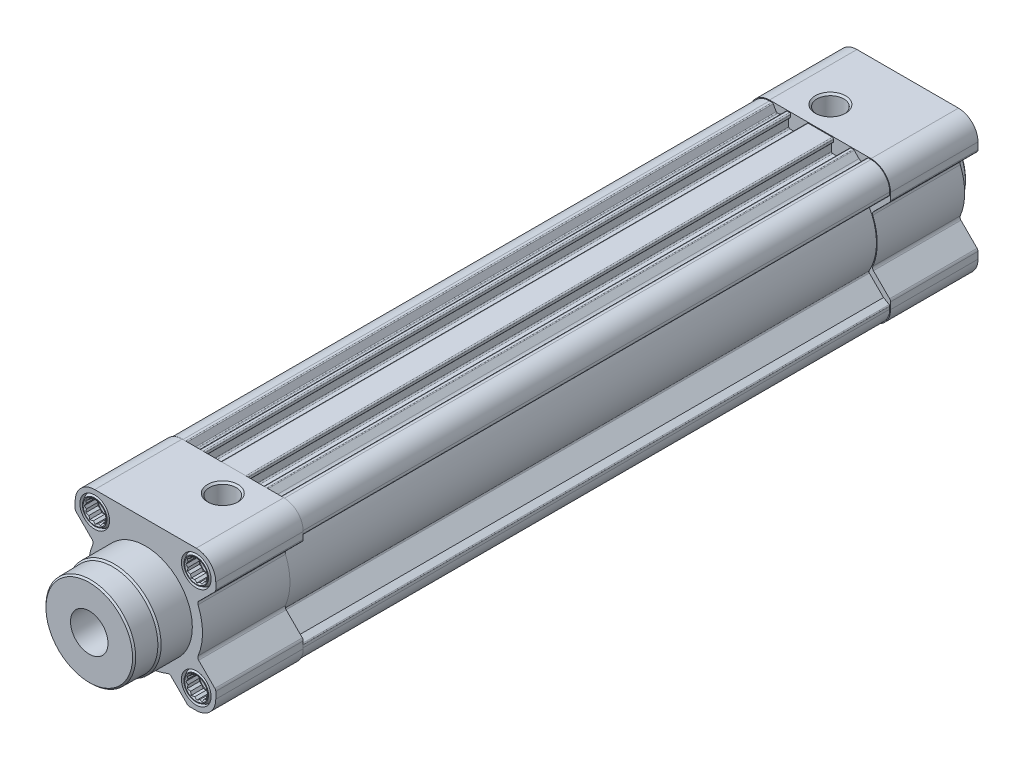
SolidWorks part; units mm, degrees
ref_plane "Front Plane" through (0, 0, 0) normal (0, 0, 1) x (1, 0, 0)
ref_plane "Top Plane" through (0, 0, 0) normal (0, 1, 0) x (1, 0, 0)
ref_plane "Right Plane" through (0, 0, 0) normal (1, 0, 0) x (0, 0, -1)
ref_plane "Plane1" through (0, 0, -28) normal (0, 0, 1) x (1, 0, 0)
sketch "Sketch1" plane through (0, 0, -28) normal (0, 0, 1) x (1, 0, 0)
  line L0 (-22.2071, 13.3683) -> (-17.0289, 8.1901)
  line L1 (-17.0289, -8.1901) -> (-22.2071, -13.3683)
  line L2 (-22.5, -14.0754) -> (-22.5, -16.25)
  line L3 (-16.25, -22.5) -> (-14.0754, -22.5)
  line L4 (-13.3683, -22.2071) -> (-8.1901, -17.0289)
  line L5 (8.1901, -17.0289) -> (13.3683, -22.2071)
  line L6 (14.0754, -22.5) -> (16.25, -22.5)
  line L7 (22.5, -16.25) -> (22.5, -14.0754)
  line L8 (22.2071, -13.3683) -> (17.0289, -8.1901)
  line L9 (17.0289, 8.1901) -> (22.2071, 13.3683)
  line L10 (22.5, 14.0754) -> (22.5, 16.25)
  line L11 (16.25, 22.5) -> (-16.25, 22.5)
  line L12 (-22.5, 16.25) -> (-22.5, 14.0754)
  arc A0 (-22.5, 14.0754) -> (-22.2071, 13.3683) centre (-21.5, 14.0754) ccw
  arc A1 (-17.0289, 8.1901) -> (-16.8147, 7.0943) centre (-17.736, 7.483) cw
  arc A2 (-16.8147, 7.0943) -> (-16.8147, -7.0943) centre (0, 0) ccw
  arc A3 (-16.8147, -7.0943) -> (-17.0289, -8.1901) centre (-17.736, -7.483) cw
  arc A4 (-22.2071, -13.3683) -> (-22.5, -14.0754) centre (-21.5, -14.0754) ccw
  arc A5 (-22.5, -16.25) -> (-16.25, -22.5) centre (-16.25, -16.25) ccw
  arc A6 (-14.0754, -22.5) -> (-13.3683, -22.2071) centre (-14.0754, -21.5) ccw
  arc A7 (-8.1901, -17.0289) -> (-7.0943, -16.8147) centre (-7.483, -17.736) cw
  arc A8 (-7.0943, -16.8147) -> (7.0943, -16.8147) centre (0, 0) ccw
  arc A9 (7.0943, -16.8147) -> (8.1901, -17.0289) centre (7.483, -17.736) cw
  arc A10 (13.3683, -22.2071) -> (14.0754, -22.5) centre (14.0754, -21.5) ccw
  arc A11 (16.25, -22.5) -> (22.5, -16.25) centre (16.25, -16.25) ccw
  arc A12 (22.5, -14.0754) -> (22.2071, -13.3683) centre (21.5, -14.0754) ccw
  arc A13 (17.0289, -8.1901) -> (16.8147, -7.0943) centre (17.736, -7.483) cw
  arc A14 (16.8147, -7.0943) -> (16.8147, 7.0943) centre (0, 0) ccw
  arc A15 (16.8147, 7.0943) -> (17.0289, 8.1901) centre (17.736, 7.483) cw
  arc A16 (22.2071, 13.3683) -> (22.5, 14.0754) centre (21.5, 14.0754) ccw
  arc A17 (22.5, 16.25) -> (16.25, 22.5) centre (16.25, 16.25) ccw
  arc A18 (-16.25, 22.5) -> (-22.5, 16.25) centre (-16.25, 16.25) ccw
extrude "Boss-Extrude1" add sketch "Sketch1" along normal blind 28
sketch "Sketch2" plane through (0, 0, -28) normal (0, 0, 1) x (1, 0, 0)
  line L0 (-22.25, 13.7647) -> (-16.641, 8.1557)
  line L1 (-16.641, -8.1557) -> (-22.25, -13.7647)
  line L2 (-22.25, -13.7647) -> (-22.25, -16.25)
  line L3 (-16.25, -22.25) -> (-13.7647, -22.25)
  line L4 (-13.7647, -22.25) -> (-8.1557, -16.641)
  line L5 (8.1557, -16.641) -> (13.7647, -22.25)
  line L6 (13.7647, -22.25) -> (16.25, -22.25)
  line L7 (22.25, -16.25) -> (22.25, -13.7647)
  line L8 (22.25, -13.7647) -> (16.641, -8.1557)
  line L9 (16.641, 8.1557) -> (22.25, 13.7647)
  line L10 (22.25, 13.7647) -> (22.25, 16.25)
  line L11 (16.25, 22.25) -> (-16.25, 22.25)
  line L12 (-22.25, 16.25) -> (-22.25, 13.7647)
  arc A0 (-16.641, 8.1557) -> (-16.5402, 7.5936) centre (-16.9946, 7.8022) cw
  arc A1 (-16.5402, 7.5936) -> (-16.5402, -7.5936) centre (0, 0) ccw
  arc A2 (-16.5402, -7.5936) -> (-16.641, -8.1557) centre (-16.9946, -7.8022) cw
  arc A3 (-22.25, -16.25) -> (-16.25, -22.25) centre (-16.25, -16.25) ccw
  arc A4 (-8.1557, -16.641) -> (-7.5936, -16.5402) centre (-7.8022, -16.9946) cw
  arc A5 (-7.5936, -16.5402) -> (7.5936, -16.5402) centre (0, 0) ccw
  arc A6 (7.5936, -16.5402) -> (8.1557, -16.641) centre (7.8022, -16.9946) cw
  arc A7 (16.25, -22.25) -> (22.25, -16.25) centre (16.25, -16.25) ccw
  arc A8 (16.641, -8.1557) -> (16.5402, -7.5936) centre (16.9946, -7.8022) cw
  arc A9 (16.5402, -7.5936) -> (16.5402, 7.5936) centre (0, 0) ccw
  arc A10 (16.5402, 7.5936) -> (16.641, 8.1557) centre (16.9946, 7.8022) cw
  arc A11 (22.25, 16.25) -> (16.25, 22.25) centre (16.25, 16.25) ccw
  arc A12 (-16.25, 22.25) -> (-22.25, 16.25) centre (-16.25, 16.25) ccw
extrude "Boss-Extrude2" add sketch "Sketch2" against normal blind 188
sketch "Sketch3" plane through (0, 0, -28) normal (0, 0, 1) x (1, 0, 0)
  line L0 (-27, -27) -> (27, -27)
  line L1 (27, -27) -> (27, 27)
  line L2 (27, 27) -> (-27, 27)
  line L3 (-27, 27) -> (-27, -27)
  line L4 (-22.05, 15.0635) -> (-20.288, 14.0462)
  line L5 (-20.2051, 13.9826) -> (-15.7255, 9.503)
  line L6 (-15.7255, -9.503) -> (-20.2424, -14.0198)
  line L7 (-20.2424, -14.0198) -> (-22.05, -15.0635)
  line L8 (-22.25, -15.4099) -> (-22.25, -16.25)
  line L9 (-16.25, -22.25) -> (-15.4099, -22.25)
  line L10 (-15.0635, -22.05) -> (-14.0462, -20.288)
  line L11 (-13.9826, -20.2051) -> (-9.503, -15.7255)
  line L12 (9.503, -15.7255) -> (13.9826, -20.2051)
  line L13 (14.0462, -20.288) -> (15.0635, -22.05)
  line L14 (15.4099, -22.25) -> (16.25, -22.25)
  line L15 (22.25, -16.25) -> (22.25, -15.4099)
  line L16 (22.05, -15.0635) -> (20.2424, -14.0198)
  line L17 (20.2424, -14.0198) -> (15.7255, -9.503)
  line L18 (15.7255, 9.503) -> (20.2051, 13.9826)
  line L19 (20.288, 14.0462) -> (22.05, 15.0635)
  line L20 (22.25, 15.4099) -> (22.25, 16.25)
  line L21 (16.25, 22.25) -> (15.4099, 22.25)
  line L22 (15.0635, 22.05) -> (14.082, 20.35)
  line L23 (13.7356, 20.15) -> (13.4713, 20.15)
  line L24 (12.4107, 20.5893) -> (10.8672, 22.1328)
  line L25 (10.5843, 22.25) -> (9.85, 22.25)
  line L26 (9.45, 21.85) -> (9.45, 21.15)
  line L27 (9.65, 20.95) -> (9.9, 20.95)
  line L28 (10.1, 20.75) -> (10.1, 18.15)
  line L29 (9.7, 17.75) -> (4, 17.75)
  line L30 (3.6, 18.15) -> (3.6, 20.75)
  line L31 (3.8, 20.95) -> (4.05, 20.95)
  line L32 (4.25, 21.15) -> (4.25, 21.85)
  line L33 (3.85, 22.25) -> (-3.85, 22.25)
  line L34 (-4.25, 21.85) -> (-4.25, 21.15)
  line L35 (-4.05, 20.95) -> (-3.8, 20.95)
  line L36 (-3.6, 20.75) -> (-3.6, 18.15)
  line L37 (-4, 17.75) -> (-9.7, 17.75)
  line L38 (-10.1, 18.15) -> (-10.1, 20.75)
  line L39 (-9.9, 20.95) -> (-9.65, 20.95)
  line L40 (-9.45, 21.15) -> (-9.45, 21.85)
  line L41 (-9.85, 22.25) -> (-10.5843, 22.25)
  line L42 (-10.8672, 22.1328) -> (-12.4107, 20.5893)
  line L43 (-13.4713, 20.15) -> (-13.7356, 20.15)
  line L44 (-14.082, 20.35) -> (-15.0635, 22.05)
  line L45 (-15.4099, 22.25) -> (-16.25, 22.25)
  line L46 (-22.25, 16.25) -> (-22.25, 15.4099)
  arc A0 (-22.25, 15.4099) -> (-22.05, 15.0635) centre (-21.85, 15.4099) ccw
  arc A1 (-20.288, 14.0462) -> (-20.2051, 13.9826) centre (-20.488, 13.6997) cw
  arc A2 (-15.7255, 9.503) -> (-15.6445, 8.9022) centre (-16.0791, 9.1495) cw
  arc A3 (-15.6445, 8.9022) -> (-15.6445, -8.9022) centre (0, 0) ccw
  arc A4 (-15.6445, -8.9022) -> (-15.7255, -9.503) centre (-16.0791, -9.1495) cw
  arc A5 (-22.05, -15.0635) -> (-22.25, -15.4099) centre (-21.85, -15.4099) ccw
  arc A6 (-22.25, -16.25) -> (-16.25, -22.25) centre (-16.25, -16.25) ccw
  arc A7 (-15.4099, -22.25) -> (-15.0635, -22.05) centre (-15.4099, -21.85) ccw
  arc A8 (-14.0462, -20.288) -> (-13.9826, -20.2051) centre (-13.6997, -20.488) cw
  arc A9 (-9.503, -15.7255) -> (-8.9022, -15.6445) centre (-9.1495, -16.0791) cw
  arc A10 (-8.9022, -15.6445) -> (8.9022, -15.6445) centre (0, 0) ccw
  arc A11 (8.9022, -15.6445) -> (9.503, -15.7255) centre (9.1495, -16.0791) cw
  arc A12 (13.9826, -20.2051) -> (14.0462, -20.288) centre (13.6997, -20.488) cw
  arc A13 (15.0635, -22.05) -> (15.4099, -22.25) centre (15.4099, -21.85) ccw
  arc A14 (16.25, -22.25) -> (22.25, -16.25) centre (16.25, -16.25) ccw
  arc A15 (22.25, -15.4099) -> (22.05, -15.0635) centre (21.85, -15.4099) ccw
  arc A16 (15.7255, -9.503) -> (15.6445, -8.9022) centre (16.0791, -9.1495) cw
  arc A17 (15.6445, -8.9022) -> (15.6445, 8.9022) centre (0, 0) ccw
  arc A18 (15.6445, 8.9022) -> (15.7255, 9.503) centre (16.0791, 9.1495) cw
  arc A19 (20.2051, 13.9826) -> (20.288, 14.0462) centre (20.488, 13.6997) cw
  arc A20 (22.05, 15.0635) -> (22.25, 15.4099) centre (21.85, 15.4099) ccw
  arc A21 (22.25, 16.25) -> (16.25, 22.25) centre (16.25, 16.25) ccw
  arc A22 (15.4099, 22.25) -> (15.0635, 22.05) centre (15.4099, 21.85) ccw
  arc A23 (14.082, 20.35) -> (13.7356, 20.15) centre (13.7356, 20.55) cw
  arc A24 (13.4713, 20.15) -> (12.4107, 20.5893) centre (13.4713, 21.65) cw
  arc A25 (10.8672, 22.1328) -> (10.5843, 22.25) centre (10.5843, 21.85) ccw
  arc A26 (9.85, 22.25) -> (9.45, 21.85) centre (9.85, 21.85) ccw
  arc A27 (9.45, 21.15) -> (9.65, 20.95) centre (9.65, 21.15) ccw
  arc A28 (9.9, 20.95) -> (10.1, 20.75) centre (9.9, 20.75) cw
  arc A29 (10.1, 18.15) -> (9.7, 17.75) centre (9.7, 18.15) cw
  arc A30 (4, 17.75) -> (3.6, 18.15) centre (4, 18.15) cw
  arc A31 (3.6, 20.75) -> (3.8, 20.95) centre (3.8, 20.75) cw
  arc A32 (4.05, 20.95) -> (4.25, 21.15) centre (4.05, 21.15) ccw
  arc A33 (4.25, 21.85) -> (3.85, 22.25) centre (3.85, 21.85) ccw
  arc A34 (-3.85, 22.25) -> (-4.25, 21.85) centre (-3.85, 21.85) ccw
  arc A35 (-4.25, 21.15) -> (-4.05, 20.95) centre (-4.05, 21.15) ccw
  arc A36 (-3.8, 20.95) -> (-3.6, 20.75) centre (-3.8, 20.75) cw
  arc A37 (-3.6, 18.15) -> (-4, 17.75) centre (-4, 18.15) cw
  arc A38 (-9.7, 17.75) -> (-10.1, 18.15) centre (-9.7, 18.15) cw
  arc A39 (-10.1, 20.75) -> (-9.9, 20.95) centre (-9.9, 20.75) cw
  arc A40 (-9.65, 20.95) -> (-9.45, 21.15) centre (-9.65, 21.15) ccw
  arc A41 (-9.45, 21.85) -> (-9.85, 22.25) centre (-9.85, 21.85) ccw
  arc A42 (-10.5843, 22.25) -> (-10.8672, 22.1328) centre (-10.5843, 21.85) ccw
  arc A43 (-12.4107, 20.5893) -> (-13.4713, 20.15) centre (-13.4713, 21.65) cw
  arc A44 (-13.7356, 20.15) -> (-14.082, 20.35) centre (-13.7356, 20.55) cw
  arc A45 (-15.0635, 22.05) -> (-15.4099, 22.25) centre (-15.4099, 21.85) ccw
  arc A46 (-16.25, 22.25) -> (-22.25, 16.25) centre (-16.25, 16.25) ccw
extrude "Cut-Extrude1" cut sketch "Sketch3" against normal blind 188
ref_plane "Plane2" through (0, 0, -244) normal (0, 0, 1) x (1, 0, 0)
sketch "Sketch4" plane through (0, 0, -244) normal (0, 0, 1) x (1, 0, 0)
  line L0 (-22.2071, 13.3683) -> (-17.0289, 8.1901)
  line L1 (-17.0289, -8.1901) -> (-22.2071, -13.3683)
  line L2 (-22.5, -14.0754) -> (-22.5, -16.25)
  line L3 (-16.25, -22.5) -> (-14.0754, -22.5)
  line L4 (-13.3683, -22.2071) -> (-8.1901, -17.0289)
  line L5 (8.1901, -17.0289) -> (13.3683, -22.2071)
  line L6 (14.0754, -22.5) -> (16.25, -22.5)
  line L7 (22.5, -16.25) -> (22.5, -14.0754)
  line L8 (22.2071, -13.3683) -> (17.0289, -8.1901)
  line L9 (17.0289, 8.1901) -> (22.2071, 13.3683)
  line L10 (22.5, 14.0754) -> (22.5, 16.25)
  line L11 (16.25, 22.5) -> (-16.25, 22.5)
  line L12 (-22.5, 16.25) -> (-22.5, 14.0754)
  arc A0 (-22.5, 14.0754) -> (-22.2071, 13.3683) centre (-21.5, 14.0754) ccw
  arc A1 (-17.0289, 8.1901) -> (-16.8147, 7.0943) centre (-17.736, 7.483) cw
  arc A2 (-16.8147, 7.0943) -> (-16.8147, -7.0943) centre (0, 0) ccw
  arc A3 (-16.8147, -7.0943) -> (-17.0289, -8.1901) centre (-17.736, -7.483) cw
  arc A4 (-22.2071, -13.3683) -> (-22.5, -14.0754) centre (-21.5, -14.0754) ccw
  arc A5 (-22.5, -16.25) -> (-16.25, -22.5) centre (-16.25, -16.25) ccw
  arc A6 (-14.0754, -22.5) -> (-13.3683, -22.2071) centre (-14.0754, -21.5) ccw
  arc A7 (-8.1901, -17.0289) -> (-7.0943, -16.8147) centre (-7.483, -17.736) cw
  arc A8 (-7.0943, -16.8147) -> (7.0943, -16.8147) centre (0, 0) ccw
  arc A9 (7.0943, -16.8147) -> (8.1901, -17.0289) centre (7.483, -17.736) cw
  arc A10 (13.3683, -22.2071) -> (14.0754, -22.5) centre (14.0754, -21.5) ccw
  arc A11 (16.25, -22.5) -> (22.5, -16.25) centre (16.25, -16.25) ccw
  arc A12 (22.5, -14.0754) -> (22.2071, -13.3683) centre (21.5, -14.0754) ccw
  arc A13 (17.0289, -8.1901) -> (16.8147, -7.0943) centre (17.736, -7.483) cw
  arc A14 (16.8147, -7.0943) -> (16.8147, 7.0943) centre (0, 0) ccw
  arc A15 (16.8147, 7.0943) -> (17.0289, 8.1901) centre (17.736, 7.483) cw
  arc A16 (22.2071, 13.3683) -> (22.5, 14.0754) centre (21.5, 14.0754) ccw
  arc A17 (22.5, 16.25) -> (16.25, 22.5) centre (16.25, 16.25) ccw
  arc A18 (-16.25, 22.5) -> (-22.5, 16.25) centre (-16.25, 16.25) ccw
extrude "Boss-Extrude3" add sketch "Sketch4" along normal blind 28
sketch "Sketch5" plane through (0, 0, 0) normal (1, 0, 0) x (0, 0, -1)
  line L0 (-18, 0) -> (-18, 13.8691)
  line L1 (-18, 13.8691) -> (-17.5, 14.3691)
  line L2 (-17.5, 14.3691) -> (-10.5089, 14.4911)
  line L3 (-10.5089, 14.4911) -> (-10, 15)
  line L4 (-10, 15) -> (0, 15)
  line L5 (0, 15) -> (0, 0)
  line L6 (0, 0) -> (-18, 0)
  line L7 (0, 0) -> (-18, 0) construction
revolve "Revolve1" add sketch "Sketch5" angle 360 about L7 reverse direction yes
ref_plane "Plane3" through (5.25, 0, 0) normal (1, 0, 0) x (0, 0, -1)
sketch "Sketch6" plane through (5.25, 0, 0) normal (1, 0, 0) x (0, 0, -1)
  line L0 (19.5, 22.5) -> (24.364, 22.5)
  line L1 (24.364, 22.5) -> (23.783, 21.919)
  line L2 (23.783, 21.919) -> (23.783, 0)
  line L3 (23.783, 0) -> (19.5, 0)
  line L4 (19.5, 0) -> (19.5, 22.5)
  line L5 (19.5, 0) -> (19.5, 22.5) construction
revolve "Cut-Revolve1" cut sketch "Sketch6" angle 360 about L5 reverse direction yes
cosmetic thread "Cosmetic Thread1" parameters "D1"=10, "D2"=9.728
ref_plane "Plane4" through (-5.7, 0, 0) normal (1, 0, 0) x (0, 0, -1)
ref_plane "Plane5" through (16.25, 0, 0) normal (1, 0, 0) x (0, 0, -1)
sketch "Sketch7" plane through (16.25, 0, 0) normal (1, 0, 0) x (0, 0, -1)
  line L0 (0, 16.25) -> (0, 21)
  line L1 (0, 21) -> (21, 21)
  line L2 (21, 21) -> (21, 16.25)
  line L3 (21, 16.25) -> (0, 16.25)
  line L4 (21, 16.25) -> (0, 16.25) construction
revolve "Cut-Revolve2" cut sketch "Sketch7" angle 360 about L4 reverse direction yes
sketch "Sketch8" plane through (0, 0, 0) normal (0, 0, 1) x (1, 0, 0)
  line L0 (16.25, 16.25) -> (-16.25, 16.25)
  line L1 (16.25, 16.25) -> (16.25, -16.25)
pattern_linear "LPattern1" count 2 spacing 32.5 along (-1, 0, 0) count 2 spacing 32.5 along (0, -1, 0) of "Cut-Revolve2"
sketch "Sketch9" plane through (16.25, 0, 0) normal (1, 0, 0) x (0, 0, -1)
  line L0 (0, 16.25) -> (0, 20.1726)
  line L1 (0, 20.1726) -> (1, 20.75)
  line L2 (1, 20.75) -> (21, 20.75)
  line L3 (21, 20.75) -> (21, 16.25)
  line L4 (21, 16.25) -> (0, 16.25)
  line L5 (21, 16.25) -> (0, 16.25) construction
revolve "Revolve2" add sketch "Sketch9" angle 360 about L5 reverse direction yes
sketch "Sketch10" plane through (0, 0, 0) normal (0, 0, 1) x (1, 0, 0)
  line L0 (16.25, 16.25) -> (-16.25, 16.25)
  line L1 (16.25, 16.25) -> (16.25, -16.25)
pattern_linear "LPattern2" count 2 spacing 32.5 along (-1, 0, 0) count 2 spacing 32.5 along (0, -1, 0) of "Revolve2"
sketch "Sketch11" plane through (16.25, 0, 0) normal (1, 0, 0) x (0, 0, -1)
  line L0 (0, 16.25) -> (0, 19.95)
  line L1 (0, 19.95) -> (0.4041, 19.25)
  line L2 (0.4041, 19.25) -> (5.5, 19.25)
  line L3 (5.5, 19.25) -> (6.0415, 18.7085)
  line L4 (6.0415, 18.7085) -> (18.7, 18.7085)
  line L5 (18.7, 18.7085) -> (20.1194, 16.25)
  line L6 (20.1194, 16.25) -> (0, 16.25)
  line L7 (20.1194, 16.25) -> (0, 16.25) construction
revolve "Cut-Revolve3" cut sketch "Sketch11" angle 360 about L7 reverse direction yes
cosmetic thread "Cosmetic Thread2" parameters "D1"=10.5, "D2"=6
sketch "Sketch12" plane through (0, 0, 0) normal (0, 0, 1) x (1, 0, 0)
  line L0 (12.7859, 16.25) -> (13.25, 15.4462)
  line L1 (13.25, 15.4462) -> (13.25, 14.5179)
  line L2 (13.25, 14.5179) -> (14.0538, 14.0538)
  line L3 (14.0538, 14.0538) -> (14.5179, 13.25)
  line L4 (14.5179, 13.25) -> (15.4462, 13.25)
  line L5 (15.4462, 13.25) -> (16.25, 12.7859)
  line L6 (16.25, 12.7859) -> (17.0538, 13.25)
  line L7 (17.0538, 13.25) -> (17.9821, 13.25)
  line L8 (17.9821, 13.25) -> (18.4462, 14.0538)
  line L9 (18.4462, 14.0538) -> (19.25, 14.5179)
  line L10 (19.25, 14.5179) -> (19.25, 15.4462)
  line L11 (19.25, 15.4462) -> (19.7141, 16.25)
  line L12 (19.7141, 16.25) -> (19.25, 17.0538)
  line L13 (19.25, 17.0538) -> (19.25, 17.9821)
  line L14 (19.25, 17.9821) -> (18.4462, 18.4462)
  line L15 (18.4462, 18.4462) -> (17.9821, 19.25)
  line L16 (17.9821, 19.25) -> (17.0538, 19.25)
  line L17 (17.0538, 19.25) -> (16.25, 19.7141)
  line L18 (16.25, 19.7141) -> (15.4462, 19.25)
  line L19 (15.4462, 19.25) -> (14.5179, 19.25)
  line L20 (14.5179, 19.25) -> (14.0538, 18.4462)
  line L21 (14.0538, 18.4462) -> (13.25, 17.9821)
  line L22 (13.25, 17.9821) -> (13.25, 17.0538)
  line L23 (13.25, 17.0538) -> (12.7859, 16.25)
extrude "Cut-Extrude2" cut sketch "Sketch12" along normal blind 4 and the other way blind 4
sketch "Sketch13" plane through (0, 0, 0) normal (0, 0, 1) x (1, 0, 0)
  line L0 (16.25, 16.25) -> (-16.25, 16.25)
  line L1 (16.25, 16.25) -> (16.25, -16.25)
pattern_linear "LPattern3" count 2 spacing 32.5 along (-1, 0, 0) count 2 spacing 32.5 along (0, -1, 0) of "Cut-Revolve3"
cosmetic thread "Cosmetic Thread3" parameters "D1"=10.5, "D2"=6
cosmetic thread "Cosmetic Thread4" parameters "D1"=10.5, "D2"=6
cosmetic thread "Cosmetic Thread5" parameters "D1"=10.5, "D2"=6
sketch "Sketch14" plane through (0, 0, 0) normal (0, 0, 1) x (1, 0, 0)
  line L0 (16.25, 16.25) -> (-16.25, 16.25)
  line L1 (16.25, 16.25) -> (16.25, -16.25)
pattern_linear "LPattern4" count 2 spacing 32.5 along (-1, 0, 0) count 2 spacing 32.5 along (0, -1, 0) of "Cut-Extrude2"
ref_plane "Plane6" through (0, 0, -244) normal (0, 0, 1) x (1, 0, 0)
sketch "Sketch15" plane through (0, 0, 0) normal (1, 0, 0) x (0, 0, -1)
  line L0 (244, 0) -> (244, 15)
  line L1 (244, 15) -> (247.5, 15)
  line L2 (247.5, 15) -> (248, 14.5)
  line L3 (248, 14.5) -> (248, 0)
  line L4 (248, 0) -> (244, 0)
  line L5 (248, 0) -> (244, 0) construction
revolve "Revolve3" add sketch "Sketch15" angle 360 about L5 reverse direction yes
ref_plane "Plane7" through (-5.25, 0, 0) normal (1, 0, 0) x (0, 0, -1)
sketch "Sketch16" plane through (-5.25, 0, 0) normal (1, 0, 0) x (0, 0, -1)
  line L0 (224.5, 22.5) -> (229.364, 22.5)
  line L1 (229.364, 22.5) -> (228.783, 21.919)
  line L2 (228.783, 21.919) -> (228.783, 0)
  line L3 (228.783, 0) -> (224.5, 0)
  line L4 (224.5, 0) -> (224.5, 22.5)
  line L5 (224.5, 0) -> (224.5, 22.5) construction
revolve "Cut-Revolve4" cut sketch "Sketch16" angle 360 about L5 reverse direction yes
cosmetic thread "Cosmetic Thread6" parameters "D1"=10, "D2"=9.728
ref_plane "Plane8" through (5.7, 0, 0) normal (1, 0, 0) x (0, 0, -1)
sketch "Sketch17" plane through (16.25, 0, 0) normal (1, 0, 0) x (0, 0, -1)
  line L0 (223, 16.25) -> (223, 21)
  line L1 (223, 21) -> (244, 21)
  line L2 (244, 21) -> (244, 16.25)
  line L3 (244, 16.25) -> (223, 16.25)
  line L4 (244, 16.25) -> (223, 16.25) construction
revolve "Cut-Revolve5" cut sketch "Sketch17" angle 360 about L4 reverse direction yes
sketch "Sketch18" plane through (0, 0, -244) normal (0, 0, 1) x (1, 0, 0)
  line L0 (16.25, 16.25) -> (-16.25, 16.25)
  line L1 (16.25, 16.25) -> (16.25, -16.25)
pattern_linear "LPattern5" count 2 spacing 32.5 along (-1, 0, 0) count 2 spacing 32.5 along (0, -1, 0) of "Cut-Revolve5"
sketch "Sketch19" plane through (16.25, 0, 0) normal (1, 0, 0) x (0, 0, -1)
  line L0 (223, 16.25) -> (223, 20.75)
  line L1 (223, 20.75) -> (243, 20.75)
  line L2 (243, 20.75) -> (244, 20.1726)
  line L3 (244, 20.1726) -> (244, 16.25)
  line L4 (244, 16.25) -> (223, 16.25)
  line L5 (244, 16.25) -> (223, 16.25) construction
revolve "Revolve4" add sketch "Sketch19" angle 360 about L5 reverse direction yes
sketch "Sketch20" plane through (0, 0, -244) normal (0, 0, 1) x (1, 0, 0)
  line L0 (16.25, 16.25) -> (-16.25, 16.25)
  line L1 (16.25, 16.25) -> (16.25, -16.25)
pattern_linear "LPattern6" count 2 spacing 32.5 along (-1, 0, 0) count 2 spacing 32.5 along (0, -1, 0) of "Revolve4"
sketch "Sketch21" plane through (16.25, 0, 0) normal (1, 0, 0) x (0, 0, -1)
  line L0 (223.8806, 16.25) -> (225.3, 18.7085)
  line L1 (225.3, 18.7085) -> (237.9585, 18.7085)
  line L2 (237.9585, 18.7085) -> (238.5, 19.25)
  line L3 (238.5, 19.25) -> (243.5959, 19.25)
  line L4 (243.5959, 19.25) -> (244, 19.95)
  line L5 (244, 19.95) -> (244, 16.25)
  line L6 (244, 16.25) -> (223.8806, 16.25)
  line L7 (244, 16.25) -> (223.8806, 16.25) construction
revolve "Cut-Revolve6" cut sketch "Sketch21" angle 360 about L7 reverse direction yes
cosmetic thread "Cosmetic Thread7" parameters "D1"=10.5, "D2"=6
sketch "Sketch22" plane through (0, 0, -244) normal (0, 0, 1) x (1, 0, 0)
  line L0 (16.25, 16.25) -> (-16.25, 16.25)
  line L1 (16.25, 16.25) -> (16.25, -16.25)
pattern_linear "LPattern7" count 2 spacing 32.5 along (-1, 0, 0) count 2 spacing 32.5 along (0, -1, 0) of "Cut-Revolve6"
cosmetic thread "Cosmetic Thread8" parameters "D1"=10.5, "D2"=6
cosmetic thread "Cosmetic Thread9" parameters "D1"=10.5, "D2"=6
cosmetic thread "Cosmetic Thread10" parameters "D1"=10.5, "D2"=6
sketch "Sketch23" plane through (0, 0, -244) normal (0, 0, 1) x (1, 0, 0)
  line L0 (12.7859, 16.25) -> (13.25, 15.4462)
  line L1 (13.25, 15.4462) -> (13.25, 14.5179)
  line L2 (13.25, 14.5179) -> (14.0538, 14.0538)
  line L3 (14.0538, 14.0538) -> (14.5179, 13.25)
  line L4 (14.5179, 13.25) -> (15.4462, 13.25)
  line L5 (15.4462, 13.25) -> (16.25, 12.7859)
  line L6 (16.25, 12.7859) -> (17.0538, 13.25)
  line L7 (17.0538, 13.25) -> (17.9821, 13.25)
  line L8 (17.9821, 13.25) -> (18.4462, 14.0538)
  line L9 (18.4462, 14.0538) -> (19.25, 14.5179)
  line L10 (19.25, 14.5179) -> (19.25, 15.4462)
  line L11 (19.25, 15.4462) -> (19.7141, 16.25)
  line L12 (19.7141, 16.25) -> (19.25, 17.0538)
  line L13 (19.25, 17.0538) -> (19.25, 17.9821)
  line L14 (19.25, 17.9821) -> (18.4462, 18.4462)
  line L15 (18.4462, 18.4462) -> (17.9821, 19.25)
  line L16 (17.9821, 19.25) -> (17.0538, 19.25)
  line L17 (17.0538, 19.25) -> (16.25, 19.7141)
  line L18 (16.25, 19.7141) -> (15.4462, 19.25)
  line L19 (15.4462, 19.25) -> (14.5179, 19.25)
  line L20 (14.5179, 19.25) -> (14.0538, 18.4462)
  line L21 (14.0538, 18.4462) -> (13.25, 17.9821)
  line L22 (13.25, 17.9821) -> (13.25, 17.0538)
  line L23 (13.25, 17.0538) -> (12.7859, 16.25)
extrude "Cut-Extrude3" cut sketch "Sketch23" along normal blind 4 and the other way blind 4
sketch "Sketch24" plane through (0, 0, -244) normal (0, 0, 1) x (1, 0, 0)
  line L0 (16.25, 16.25) -> (-16.25, 16.25)
  line L1 (16.25, 16.25) -> (16.25, -16.25)
pattern_linear "LPattern8" count 2 spacing 32.5 along (-1, 0, 0) count 2 spacing 32.5 along (0, -1, 0) of "Cut-Extrude3"
ref_plane "Plane9" through (0, 0, 0) normal (0.7071, 0.7071, 0) x (0.7071, -0.7071, 0)
ref_plane "Plane10" through (0, 0, -254) normal (0, 0, 1) x (1, 0, 0)
ref_plane "Plane11" through (0, 0, -216) normal (0, 0, 1) x (1, 0, 0)
sketch "Sketch25" plane through (0, 0, 0) normal (1, 0, 0) x (0, 0, -1)
  line L0 (-18, 0) -> (-18, 6)
  line L1 (-18, 6) -> (55.3333, 6)
  line L2 (55.3333, 6) -> (55.3333, 16)
  line L3 (55.3333, 16) -> (216, 16)
  line L4 (216, 16) -> (216, 0)
  line L5 (216, 0) -> (-18, 0)
  line L6 (216, 0) -> (-18, 0) construction
revolve "Cut-Revolve7" cut sketch "Sketch25" angle 360 about L6 reverse direction yes
ref_plane "Plane12" through (0, 0, 18) normal (0, 0, 1) x (1, 0, 0)
ref_plane "Plane13" through (0, 0, 0) normal (0, 0, 1) x (1, 0, 0)
ref_plane "Plane14" through (0, 0, -244) normal (0, 0, 1) x (1, 0, 0)
ref_plane "Plane15" through (0, 0, -43) normal (0, 0, 1) x (1, 0, 0)
ref_plane "Plane16" through (0, 22.5, 0) normal (0, 1, 0) x (1, 0, 0)
ref_plane "Plane17" through (0, 0, -28) normal (0, 0, 1) x (1, 0, 0)
ref_plane "Plane18" through (0, 0, 0) normal (1, 0, 0) x (0, 0, -1)
ref_plane "Plane19" through (0, 22.5, 0) normal (0, 1, 0) x (1, 0, 0)
ref_plane "Plane20" through (0, 0, 0) normal (0, 0, 1) x (1, 0, 0)
ref_plane "Plane21" through (0, 0, -244) normal (0, 0, 1) x (1, 0, 0)
ref_plane "2DUMMY XY" through (0, 0, 0) normal (0, 0, -1) x (-1, 0, 0)
ref_plane "2DUMMY XZ" through (0, 0, 0) normal (0, 1, 0) x (1, 0, 0)
ref_plane "2DUMMY YZ" through (0, 0, 0) normal (1, 0, 0) x (0, 0, -1)
ref_axis "2DUMMY X" through (-80.9, 0, 0) along (1, 0, 0)
ref_axis "2DUMMY Y" through (0, 50, 0) along (0, -1, 0)
ref_axis "2DUMMY Z" through (0, 0, -80.9) along (0, 0, 1)
sketch3d "2DUMMY"
  point P0 (0, 0, 0)
ref_plane "2P XY" through (0, 0, -216) normal (0, 0, 1) x (1, 0, 0)
ref_plane "2P XZ" through (0, 0, 0) normal (0, -1, 0) x (-1, 0, 0)
ref_plane "2P YZ" through (0, 0, 0) normal (1, 0, 0) x (0, 0, -1)
ref_axis "2P X" through (-80.9, 0, -216) along (1, 0, 0)
ref_axis "2P Y" through (0, -50, -216) along (0, 1, 0)
ref_axis "2P Z" through (0, 0, 80.9) along (0, 0, -1)
sketch3d "2P"
  point P0 (0, 0, -216)
ref_plane "FDT_FRONT XY" through (0, 0, 0) normal (0, 0, 1) x (1, 0, 0)
ref_plane "FDT_FRONT XZ" through (0, 0, 0) normal (0, -1, 0) x (-1, 0, 0)
ref_plane "FDT_FRONT YZ" through (0, 0, 0) normal (1, 0, 0) x (0, 0, -1)
ref_axis "FDT_FRONT X" through (-80.9, 0, 0) along (1, 0, 0)
ref_axis "FDT_FRONT Y" through (0, -50, 0) along (0, 1, 0)
ref_axis "FDT_FRONT Z" through (0, 0, 80.9) along (0, 0, -1)
sketch3d "FDT_FRONT"
  point P0 (0, 0, 0)
ref_plane "FDT_QSFRONT XY" through (0, 22.5, 0) normal (0, 1, 0) x (1, 0, 0)
ref_plane "FDT_QSFRONT XZ" through (0, 0, -19.5) normal (0, 0, 1) x (1, 0, 0)
ref_plane "FDT_QSFRONT YZ" through (5.25, 0, 0) normal (1, 0, 0) x (0, 0, -1)
ref_axis "FDT_QSFRONT X" through (-80.9, 22.5, -19.5) along (1, 0, 0)
ref_axis "FDT_QSFRONT Y" through (5.25, 22.5, 50) along (0, 0, -1)
ref_axis "FDT_QSFRONT Z" through (5.25, 50, -19.5) along (0, -1, 0)
sketch3d "FDT_QSFRONT"
  point P0 (5.25, 22.5, -19.5)
ref_plane "FDT_QSREAR XY" through (0, 22.5, 0) normal (0, 1, 0) x (1, 0, 0)
ref_plane "FDT_QSREAR XZ" through (0, 0, -224.5) normal (0, 0, 1) x (1, 0, 0)
ref_plane "FDT_QSREAR YZ" through (-5.25, 0, 0) normal (1, 0, 0) x (0, 0, -1)
ref_axis "FDT_QSREAR X" through (-80.9, 22.5, -224.5) along (1, 0, 0)
ref_axis "FDT_QSREAR Y" through (-5.25, 22.5, 50) along (0, 0, -1)
ref_axis "FDT_QSREAR Z" through (-5.25, 50, -224.5) along (0, -1, 0)
sketch3d "FDT_QSREAR"
  point P0 (-5.25, 22.5, -224.5)
ref_plane "FDT_REAR XY" through (0, 0, -244) normal (0, 0, 1) x (1, 0, 0)
ref_plane "FDT_REAR XZ" through (0, 0, 0) normal (0, -1, 0) x (-1, 0, 0)
ref_plane "FDT_REAR YZ" through (0, 0, 0) normal (1, 0, 0) x (0, 0, -1)
ref_axis "FDT_REAR X" through (-80.9, 0, -244) along (1, 0, 0)
ref_axis "FDT_REAR Y" through (0, -50, -244) along (0, 1, 0)
ref_axis "FDT_REAR Z" through (0, 0, 80.9) along (0, 0, -1)
sketch3d "FDT_REAR"
  point P0 (0, 0, -244)
ref_plane "FDT_SLOT1 XY" through (0, 17.75, 0) normal (0, 1, 0) x (1, 0, 0)
ref_plane "FDT_SLOT1 XZ" through (0, 0, -122) normal (0, 0, 1) x (1, 0, 0)
ref_plane "FDT_SLOT1 YZ" through (6.85, 0, 0) normal (1, 0, 0) x (0, 0, -1)
ref_axis "FDT_SLOT1 X" through (-80.9, 17.75, -122) along (1, 0, 0)
ref_axis "FDT_SLOT1 Y" through (6.85, 17.75, 50) along (0, 0, -1)
ref_axis "FDT_SLOT1 Z" through (6.85, 50, -122) along (0, -1, 0)
sketch3d "FDT_SLOT1"
  point P0 (6.85, 17.75, -122)
ref_plane "FDT_SLOT2 XY" through (0, 17.75, 0) normal (0, 1, 0) x (1, 0, 0)
ref_plane "FDT_SLOT2 XZ" through (0, 0, -122) normal (0, 0, 1) x (1, 0, 0)
ref_plane "FDT_SLOT2 YZ" through (-6.85, 0, 0) normal (1, 0, 0) x (0, 0, -1)
ref_axis "FDT_SLOT2 X" through (-80.9, 17.75, -122) along (1, 0, 0)
ref_axis "FDT_SLOT2 Y" through (-6.85, 17.75, 50) along (0, 0, -1)
ref_axis "FDT_SLOT2 Z" through (-6.85, 50, -122) along (0, -1, 0)
sketch3d "FDT_SLOT2"
  point P0 (-6.85, 17.75, -122)
ref_plane "FDT_TRUNNMOUNT XY" through (0, 0, -43) normal (0, 0, 1) x (1, 0, 0)
ref_plane "FDT_TRUNNMOUNT XZ" through (0, 0, 0) normal (0, -1, 0) x (-1, 0, 0)
ref_plane "FDT_TRUNNMOUNT YZ" through (0, 0, 0) normal (1, 0, 0) x (0, 0, -1)
ref_axis "FDT_TRUNNMOUNT X" through (-80.9, 0, -43) along (1, 0, 0)
ref_axis "FDT_TRUNNMOUNT Y" through (0, -50, -43) along (0, 1, 0)
ref_axis "FDT_TRUNNMOUNT Z" through (0, 0, 80.9) along (0, 0, -1)
sketch3d "FDT_TRUNNMOUNT"
  point P0 (0, 0, -43)
ref_plane "TO_C XY" through (0, 0, -244) normal (0, 0, 1) x (1, 0, 0)
ref_plane "TO_C XZ" through (0, 0, 0) normal (0, -1, 0) x (-1, 0, 0)
ref_plane "TO_C YZ" through (0, 0, 0) normal (1, 0, 0) x (0, 0, -1)
ref_axis "TO_C X" through (-80.9, 0, -244) along (1, 0, 0)
ref_axis "TO_C Y" through (0, -50, -244) along (0, 1, 0)
ref_axis "TO_C Z" through (0, 0, 80.9) along (0, 0, -1)
sketch3d "TO_C"
  point P0 (0, 0, -244)
ref_plane "TO_P2 XY" through (0, 0, 18) normal (0, 0, 1) x (1, 0, 0)
ref_plane "TO_P2 XZ" through (0, 0, 0) normal (0, -1, 0) x (-1, 0, 0)
ref_plane "TO_P2 YZ" through (0, 0, 0) normal (1, 0, 0) x (0, 0, -1)
ref_axis "TO_P2 X" through (-80.9, 0, 18) along (1, 0, 0)
ref_axis "TO_P2 Y" through (0, -50, 18) along (0, 1, 0)
ref_axis "TO_P2 Z" through (0, 0, 80.9) along (0, 0, -1)
sketch3d "TO_P2"
  point P0 (0, 0, 18)
other "Freeze***"
